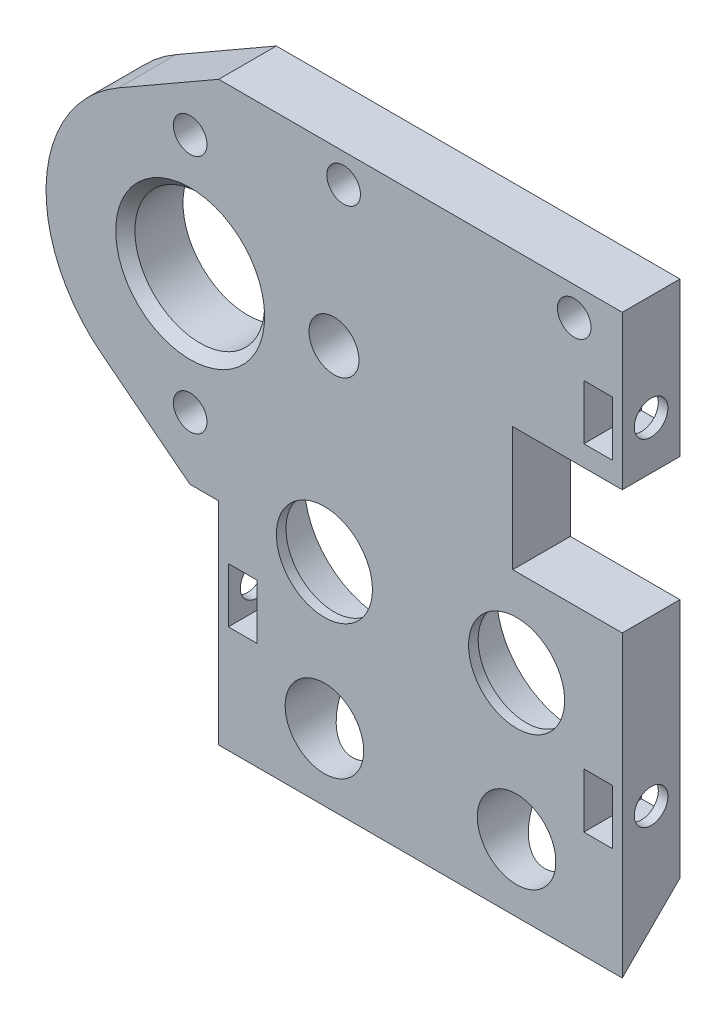
SolidWorks part; units mm, degrees
ref_plane "Front Plane" through (0, 0, 0) normal (0, 0, 1) x (1, 0, 0)
ref_plane "Top Plane" through (0, 0, 0) normal (0, 1, 0) x (1, 0, 0)
ref_plane "Right Plane" through (0, 0, 0) normal (1, 0, 0) x (0, 0, -1)
sketch "Sketch1" plane through (0, 0, 0) normal (0, 0, 1) x (1, 0, 0)
  line L0 (-21, -23) -> (21, -23) construction
  line L1 (-21, -30) -> (21, -30)
  line L2 (-21, -30) -> (-21, 30) construction
  line L3 (-21, 30) -> (21, 30)
  line L4 (21, -30) -> (21, 30)
  line L5 (-21, -30) -> (21, 30) construction
  line L6 (-21, 30) -> (21, -30) construction
  line L7 (-21, -8) -> (21, -8) construction
  line L8 (0, 0) -> (0, 14.9714) construction
  line L9 (-9, 11.975) -> (-10, -8) construction
  line L10 (-21, 30) -> (-31.4363, 24.0088)
  line L11 (-9, 11.975) -> (-23.9683, 11) construction
  line L12 (-21, -8) -> (-24, -8)
  line L13 (-21, -8) -> (-21, -30)
  line L14 (21, 27) -> (-26.2258, 27) construction
  line L15 (-24, -8) -> (-33.1948, -0.8267)
  circle A0 centre (-10, -23) radius 4.085
  circle A1 centre (-10, -8) radius 5
  circle A2 centre (10, -8) radius 5
  circle A3 centre (10, -23) radius 4.085
  circle A4 centre (-9, 11.975) radius 2.6
  circle A5 centre (-23.9683, 11) radius 2.5
  circle A6 centre (-23.9683, 11) radius 15 construction
  arc A7 (-31.4363, 24.0088) -> (-33.1948, -0.8267) centre (-23.9683, 11) ccw
  circle A8 centre (16, 27) radius 1.75
  circle A9 centre (-8, 27) radius 1.75
  point P0 (0, 0)
  point P21 (0, -8)
  dimension "D1" = 10
  dimension "D2" = 8.17
  dimension "D10" = 5.2
  dimension "D12" = 5
  dimension "D9" = 20
  dimension "D16" = 30
  dimension "D18" = 3.5
  dimension "D19" = 3.5
  dimension "D3" = 11
  dimension "D4" = 15
  dimension "D5" = 0
  dimension "D6" = 38
  dimension "D7" = 7
  dimension "D8" = 10
  dimension "D11" = 15
  dimension "D13" = 12
  dimension "D14" = 10
  dimension "D15" = 19
  dimension "D17" = 3
  dimension "D20" = 24
  dimension "D21" = 5
  dimension "D22" = 3
extrude "Boss-Extrude1" add sketch "Sketch1" along normal blind 6
sketch "Sketch2" plane through (0, 0, 6) normal (0, 0, 1) x (1, 0, 0)
  line L0 (0, 30) -> (0, 8.6133) construction
  line L1 (21, 30) -> (-21, 30) construction
  circle A0 centre (-10, -8) radius 8.085
  circle A1 centre (10, -8) radius 8.085
  dimension "D1" = 16.17
extrude "Cut-Extrude1" cut sketch "Sketch2" against normal through all from offset 1 offset against normal yes
sketch "Sketch5" plane through (0, 0, 6) normal (0, 0, 1) x (1, 0, 0)
  circle A0 centre (-23.9683, 11) radius 6.75
  dimension "D1" = 13.5
extrude "Cut-Extrude4" cut sketch "Sketch5" against normal through all
chamfer "Chamfer1" distance 6 angle 45 1 edges at (0, -30, 0)
sketch "Sketch6" plane through (0, 0, 0) normal (0, 0, -1) x (-1, 0, 0)
  line L0 (-21, -24) -> (-21, 30) construction
  line L1 (-21, 14) -> (-9.6, 14)
  line L2 (-21, 14) -> (-21, 1.1)
  line L3 (-21, 1.1) -> (-9.6, 1.1)
  line L4 (-9.6, 14) -> (-9.6, 1.1)
  line L5 (-21, 30) -> (21, 30) construction
  dimension "D1" = 11.4
  dimension "D2" = 12.9
  dimension "D3" = 16
extrude "Cut-Extrude5" cut sketch "Sketch6" against normal blind 15
sketch "Sketch7" plane through (0, 0, 0) normal (0, 0, -1) x (-1, 0, 0)
  line L0 (-21, -24) -> (-21, 1.1) construction
  line L1 (-20, -13.15) -> (-17, -13.15)
  line L2 (-20, -13.15) -> (-20, -18.85)
  line L3 (-20, -18.85) -> (-17, -18.85)
  line L4 (-17, -13.15) -> (-17, -18.85)
  line L5 (-20, -13.15) -> (-17, -18.85) construction
  line L6 (-20, -18.85) -> (-17, -13.15) construction
  line L7 (0, 0) -> (0, -4.83) construction
  line L8 (20, -18.85) -> (17, -13.15) construction
  line L9 (20, -13.15) -> (17, -18.85) construction
  line L10 (17, -13.15) -> (17, -18.85)
  line L11 (20, -18.85) -> (17, -18.85)
  line L12 (20, -13.15) -> (20, -18.85)
  line L13 (20, -13.15) -> (17, -13.15)
  line L14 (21, -30) -> (-21, -30) construction
  line L15 (-20, 21.85) -> (-17, 21.85)
  line L16 (-20, 21.85) -> (-20, 16.15)
  line L17 (-20, 16.15) -> (-17, 16.15)
  line L18 (-17, 21.85) -> (-17, 16.15)
  line L19 (-20, 21.85) -> (-17, 16.15) construction
  line L20 (-20, 16.15) -> (-17, 21.85) construction
  line L21 (23.9683, 23.5) -> (23.9683, -1.5) construction
  circle A0 centre (23.9683, 23.5) radius 1.75
  circle A1 centre (23.9683, -1.5) radius 1.75
  point P0 (-18.5, -16)
  point P14 (18.5, -16)
  point P19 (-18.5, 19)
  point P26 (23.9683, 11)
  dimension "D7" = 3.5
  dimension "D8" = 3.5
  dimension "D1" = 3
  dimension "D2" = 5.7
  dimension "D3" = 4
  dimension "D4" = 14
  dimension "D6" = 25
  dimension "D5" = 2
extrude "Cut-Extrude6" cut sketch "Sketch7" against normal blind 10
sketch "Sketch8" plane through (21, 0, 0) normal (1, 0, 0) x (0, 0, -1)
  line L0 (-6, -16) -> (0, -16) construction
  line L1 (-6, -30) -> (-6, 1.1) construction
  line L2 (0, -24) -> (0, 1.1) construction
  line L3 (-3, 19) -> (-3, 30) construction
  line L4 (-6, 30) -> (0, 30) construction
  circle A0 centre (-3, -16) radius 1.75
  circle A1 centre (-3, 19) radius 1.75
  dimension "D2" = 3.5
  dimension "D3" = 3.5
  dimension "D1" = 14
  dimension "D4" = 35
extrude "Cut-Extrude7" cut sketch "Sketch8" along normal blind 4 from offset 42 offset against normal yes
extrude "Cut-Extrude8" cut sketch "Sketch8<2>" against normal blind 4
sketch "Sketch8<2>" plane through (21, 0, 0) normal (1, 0, 0) x (0, 0, -1) same geometry as "Sketch8"
chamfer "Chamfer2" distance 1 angle 45 1 edges at (-17.2183, 11, 6)
